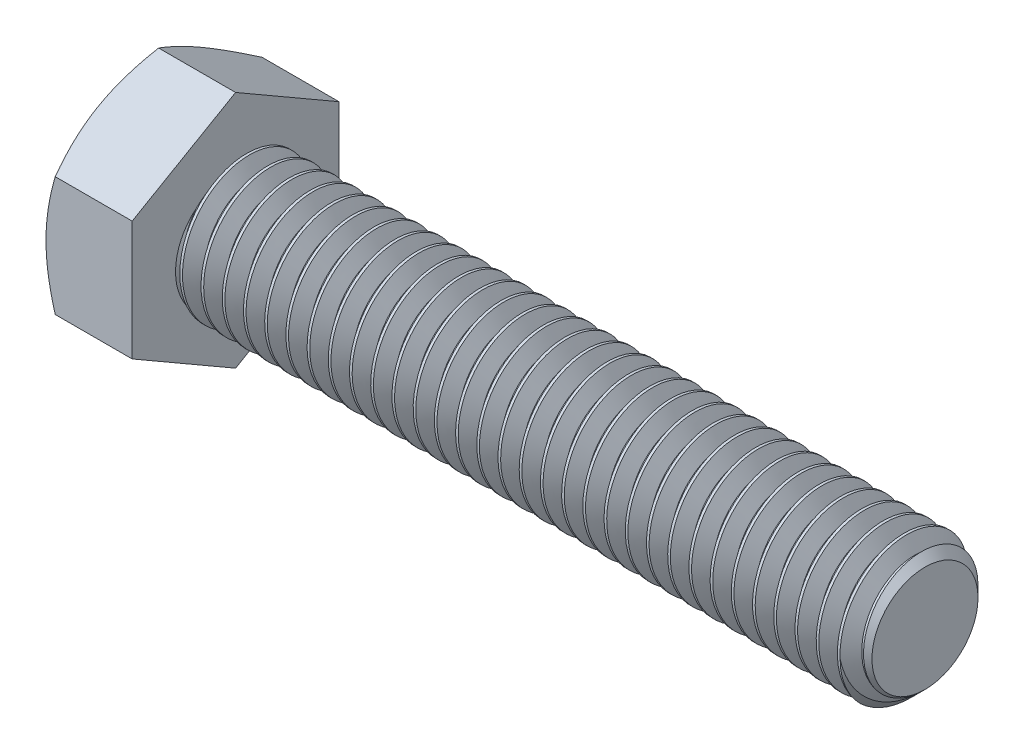
SolidWorks part; units mm, degrees
ref_plane "Front Plane" through (0, 0, 0) normal (0, 0, 1) x (1, 0, 0)
ref_plane "Top Plane" through (0, 0, 0) normal (0, 1, 0) x (1, 0, 0)
ref_plane "Right Plane" through (0, 0, 0) normal (1, 0, 0) x (0, 0, -1)
sketch "Sketch1" plane through (0, 0, 0) normal (0, 0, 1) x (1, 0, 0)
  line L0 (-35.7188, 0) -> (35.7188, 0) construction
  line L1 (35.7188, 6.35) -> (35.7188, -6.35) construction
  line L2 (-27.7813, 9.525) -> (-27.7813, -9.525) construction
  line L3 (-35.7187, 9.525) -> (-35.7187, -9.525) construction
  point P9 (-27.7812, 0)
  point P10 (28.8803, -6.35)
  dimension "D1" = 6.8385
  dimension "Screw Dia" = 12.7
  dimension "Hex" = 19.05
  dimension "Head Ht" = 7.9375
  dimension "Screw Lenght" = 63.5
ref_plane "Plane2" through (35.7188, 0, 0) normal (1, 0, 0) x (0, 0, -1)
sketch "Sketch5" plane through (35.7188, 0, 0) normal (1, 0, 0) x (0, 0, -1)
  circle A0 centre (0, 0) radius 6.35
extrude "Boss-Extrude3" add sketch "Sketch5" against normal up to vertex (63.5 mm away) up to point (-27.7812, 0, 0)
sketch "Sketch9" plane through (35.7188, 0, 0) normal (1, 0, 0) x (0, 0, -1)
  circle A1 centre (0, 0) radius 6.35
  circle A2 centre (0, 0) radius 6.35
  dimension "D1" = 0
curve "Helix/Spiral1" pitch 1.9538 height 65.4538 turns 33.5 parameters "Pitch"=1.9538
chamfer "Chamfer1" distance 1.4654 angle 45 1 edges at (35.7188, 0, -6.35)
sketch "Sketch10" plane through (0, 0, 0) normal (0, 0, 1) x (1, 0, 0)
  line L0 (35.7188, 6.35) -> (36.4514, 5.0809)
  line L1 (36.4514, 5.0809) -> (36.6957, 5.0809)
  line L2 (36.6957, 5.0809) -> (37.4284, 6.35)
  line L3 (35.7188, 6.35) -> (37.4284, 6.35)
  line L4 (36.5736, 6.35) -> (36.5736, 5.0809) construction
  line L5 (36.0851, 5.7155) -> (37.062, 5.7155) construction
  dimension "D1" = 60
  dimension "D2" = 0.2442
  dimension "D3" = 0.9769
sweep "Cut-Sweep1" cut profiles "Sketch10" path "Helix/Spiral1"
sketch "Sketch6" plane through (-27.7812, 0, 0) normal (-1, 0, 0) x (0, 0, 1)
  line L0 (0, 9.525) -> (0, -9.525) construction
  line L1 (9.525, 5.4993) -> (0, 10.9985)
  line L2 (0, 10.9985) -> (-9.525, 5.4993)
  line L3 (-9.525, 5.4993) -> (-9.525, -5.4993)
  line L4 (-9.525, -5.4993) -> (0, -10.9985)
  line L5 (0, -10.9985) -> (9.525, -5.4993)
  line L6 (9.525, -5.4993) -> (9.525, 5.4993)
  circle A0 centre (0, 0) radius 9.525 construction
extrude "Boss-Extrude4" add sketch "Sketch6" along normal up to vertex (7.9375 mm away) up to point (-35.7187, -9.525, 0)
sketch "Sketch7" plane through (-35.7187, 0, 0) normal (-1, 0, 0) x (0, 0, 1)
  circle A0 centre (0, 0) radius 9.525 construction
  circle A1 centre (0, 0) radius 9.525
sketch "Sketch8" plane through (-35.7187, 0, 0) normal (-1, 0, 0) x (0, 0, 1)
  circle A0 centre (0, 0) radius 9.525 construction
  circle A1 centre (0, 0) radius 9.525
extrude "Cut-Extrude3" cut sketch "Sketch8" against normal through all draft 60 flip side to cut
equation "\"D2@Sketch10\" = \"Pitch@Helix/Spiral1\"*.125"
equation "\"D3@Sketch10\" = \"Pitch@Helix/Spiral1\"*.5"
equation "\"D3@Helix/Spiral1\" = \"Screw Lenght@Sketch1\"+\"Pitch@Helix/Spiral1\""
equation "\"D1@Chamfer1\" = \"Pitch@Helix/Spiral1\"*.75"
equation "\"D1@Sketch1\" = \"Pitch@Helix/Spiral1\"*3.5"
